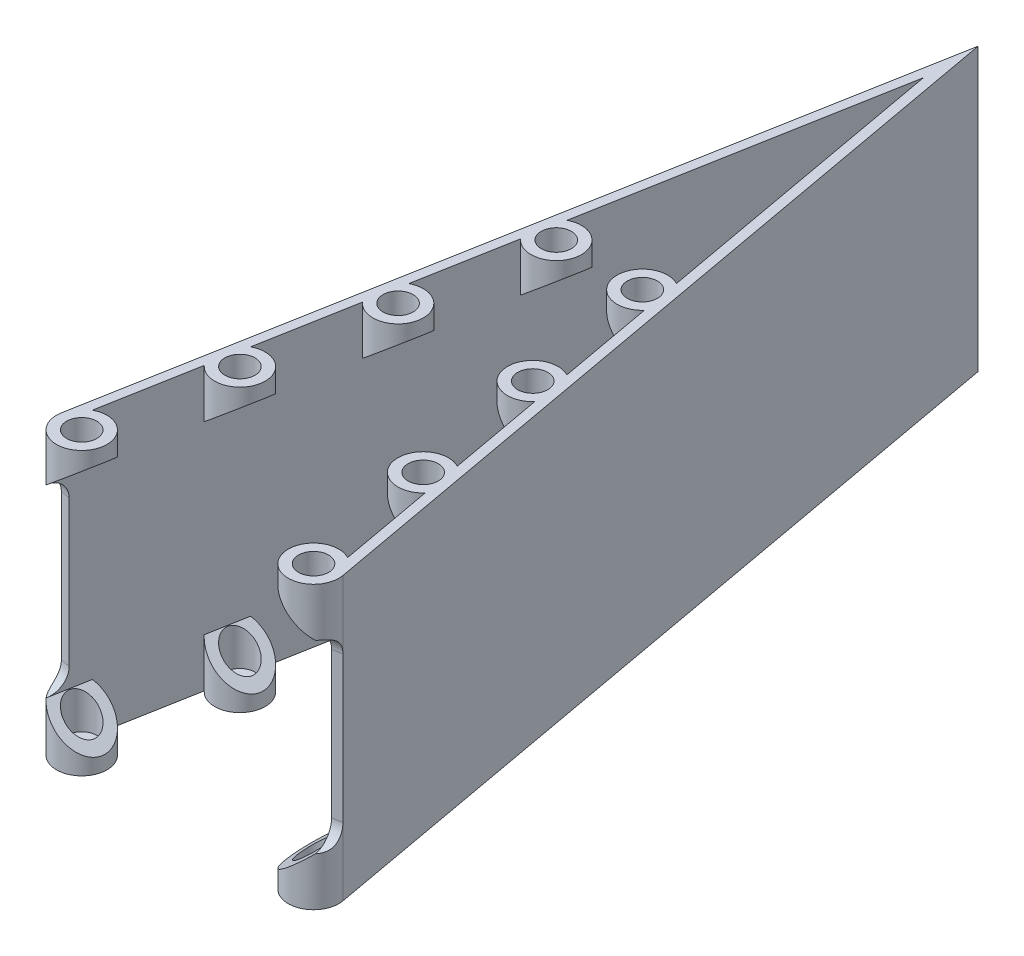
SolidWorks part; units mm, degrees
ref_plane "Front Plane" through (0, 0, 0) normal (0, 0, 1) x (1, 0, 0)
ref_plane "Top Plane" through (0, 0, 0) normal (0, 1, 0) x (1, 0, 0)
ref_plane "Right Plane" through (0, 0, 0) normal (1, 0, 0) x (0, 0, -1)
sketch "Sketch1" plane through (0, 0, 0) normal (0, 1, 0) x (1, 0, 0)
  line L0 (-13.5, 0) -> (13.5, 0) construction
  line L1 (-13.5, 0) -> (0, 74.399)
  line L2 (0, 74.399) -> (13.5, 0)
  line L3 (13.5, 0) -> (14.4839, 0.1785)
  line L4 (14.4839, 0.1785) -> (0, 80)
  line L5 (0, 80) -> (-14.4839, 0.1785)
  line L6 (-14.4839, 0.1785) -> (-13.5, 0)
  point P2 (0, 0)
  dimension "D1" = 90
  dimension "D2" = 90
  dimension "D4" = 1
  dimension "D5" = 27
  dimension "D3" = 80
extrude "Boss-Extrude1" add sketch "Sketch1" along normal blind 29
sketch "Sketch2" plane through (0, 0, 0) normal (0, 1, 0) x (1, 0, 0)
  line L0 (0, -1000) -> (0, 49000) construction
  line L1 (0, 74.399) -> (13.5, 0) construction
  line L2 (0, 74.399) -> (13.5, 0) construction
  line L3 (11.9257, -0.2857) -> (13.5, 0) construction
  line L4 (13.5, 0) -> (14.4839, 0.1785) construction
  line L5 (14.4839, 0.1785) -> (0, 80) construction
  line L6 (14.4839, 0.1785) -> (0, 80) construction
  circle A0 centre (11.9257, -0.2857) radius 2.6
  circle A1 centre (11.9257, -0.2857) radius 1.55
  circle A22 centre (9.4262, 13.4894) radius 1.55
  circle A23 centre (9.4262, 13.4894) radius 2.6
  circle A24 centre (6.9266, 27.2645) radius 1.55
  circle A25 centre (6.9266, 27.2645) radius 2.6
  circle A26 centre (4.4271, 41.0395) radius 1.55
  circle A27 centre (4.4271, 41.0395) radius 2.6
  circle A28 centre (-11.9257, -0.2857) radius 2.6
  circle A29 centre (-11.9257, -0.2857) radius 1.55
  circle A30 centre (-9.4262, 13.4894) radius 2.6
  circle A31 centre (-9.4262, 13.4894) radius 1.55
  circle A32 centre (-6.9266, 27.2645) radius 2.6
  circle A33 centre (-6.9266, 27.2645) radius 1.55
  circle A34 centre (-4.4271, 41.0395) radius 2.6
  circle A35 centre (-4.4271, 41.0395) radius 1.55
  dimension "D1" = 5.2
  dimension "D2" = 3.1
  dimension "D4" = 14
  dimension "D3" = 4
extrude "Boss-Extrude3" add sketch "Sketch2" along normal blind 5
sketch "Sketch4" plane through (0.4303, 0, 2.3715) normal (0.1785, 0, 0.9839) x (0.9839, 0, -0.1785)
  line L0 (9.0831, 5) -> (9.0831, 0) construction
  line L1 (14.2831, 5) -> (9.0831, 5) construction
  line L2 (13.2831, 29) -> (13.2831, 0) construction
  line L3 (9.0831, 5) -> (9.0831, 0) construction
  line L4 (14.2831, 5) -> (9.0831, 5) construction
  line L5 (13.2831, 29) -> (13.2831, 0) construction
  line L6 (13.2831, 5) -> (9.0831, 1.4758)
  line L7 (13.2831, 5) -> (9.0831, 5)
  line L8 (9.0831, 5) -> (9.0831, 1.4758)
  dimension "D1" = 40
extrude "Cut-Extrude1" cut sketch "Sketch4" against normal up to surface and the other way through all contours L7 L8 L6 up to face at (-8.6266, 5.4444, -26.8574)
sketch "Sketch5" plane through (-0.4303, 0, 2.3715) normal (-0.1785, 0, 0.9839) x (0.9839, 0, 0.1785)
  line L0 (-9.0831, 0) -> (-9.0831, 5) construction
  line L1 (-9.0831, 5) -> (-14.2831, 5) construction
  line L2 (-13.2831, 29) -> (-13.2831, 0) construction
  line L3 (-9.0831, 0) -> (-9.0831, 5) construction
  line L4 (-9.0831, 5) -> (-14.2831, 5) construction
  line L5 (-13.2831, 29) -> (-13.2831, 0) construction
  line L6 (-13.2831, 5) -> (-9.0831, 1.4758)
  line L7 (-13.2831, 5) -> (-9.0831, 5)
  line L8 (-9.0831, 5) -> (-9.0831, 1.4758)
  dimension "D1" = 40
extrude "Cut-Extrude2" cut sketch "Sketch5" against normal up to surface and the other way through all contours L8 L7 L6 up to face at (8.6266, 5.4444, -26.8574)
ref_plane "Plane1" through (0, 14.5, 0) normal (0, 1, 0) x (1, 0, 0)
mirror "Mirror2" about plane through (0, 14.5, 0) normal (0, 1, 0) of "Cut-Extrude2", "Cut-Extrude1", "Boss-Extrude3"
fillet "Fillet1" radius 2 4 edges at (13.992, 5, -0.0893) (13.992, 24, -0.0893) (-13.992, 24, -0.0893) (-13.992, 5, -0.0893)
sketch "Sketch6" plane through (0, 0, 0) normal (0, -1, 0) x (1, 0, 0)
  arc A0 (6.3673, -39.3087) -> (5.6355, -43.3416) centre (4.4271, -41.0395) ccw construction
  arc A1 (14.4839, -0.1785) -> (13.1341, -2.0165) centre (11.9257, 0.2857) ccw construction
  arc A2 (-5.6355, -43.3416) -> (-6.3673, -39.3087) centre (-4.4271, -41.0395) ccw construction
  arc A3 (-8.135, -29.5666) -> (-8.8668, -25.5337) centre (-6.9266, -27.2645) ccw construction
  arc A4 (8.8668, -25.5337) -> (8.135, -29.5666) centre (6.9266, -27.2645) ccw construction
  arc A5 (11.3664, -11.7586) -> (10.6346, -15.7915) centre (9.4262, -13.4894) ccw construction
  arc A6 (-10.6346, -15.7915) -> (-11.3664, -11.7586) centre (-9.4262, -13.4894) ccw construction
  arc A7 (-13.1341, -2.0165) -> (-14.4839, -0.1785) centre (-11.9257, 0.2857) ccw construction
  arc A8 (6.3673, -39.3087) -> (5.6355, -43.3416) centre (4.4271, -41.0395) ccw
  arc A9 (-5.6355, -43.3416) -> (-6.3673, -39.3087) centre (-4.4271, -41.0395) ccw
  arc A10 (-8.135, -29.5666) -> (-8.8668, -25.5337) centre (-6.9266, -27.2645) ccw
  arc A11 (14.4839, -0.1785) -> (13.1341, -2.0165) centre (11.9257, 0.2857) ccw
  arc A12 (8.8668, -25.5337) -> (8.135, -29.5666) centre (6.9266, -27.2645) ccw
  arc A13 (11.3664, -11.7586) -> (10.6346, -15.7915) centre (9.4262, -13.4894) ccw
  arc A14 (-10.6346, -15.7915) -> (-11.3664, -11.7586) centre (-9.4262, -13.4894) ccw
  arc A15 (-13.1341, -2.0165) -> (-14.4839, -0.1785) centre (-11.9257, 0.2857) ccw
  circle A16 centre (-11.9257, 0.2857) radius 2.6
  circle A17 centre (-9.4262, -13.4894) radius 2.6
  circle A18 centre (-6.9266, -27.2645) radius 2.6
  circle A19 centre (-4.4271, -41.0395) radius 2.6
  circle A28 centre (11.9257, 0.2857) radius 2.6
  circle A29 centre (4.4271, -41.0395) radius 2.6
  circle A30 centre (6.9266, -27.2645) radius 2.6
  circle A31 centre (9.4262, -13.4894) radius 2.6
extrude "Boss-Extrude4" add sketch "Sketch6" against normal blind 1
equation "\"D2@Sketch1\"=\"D1@Sketch1\""
